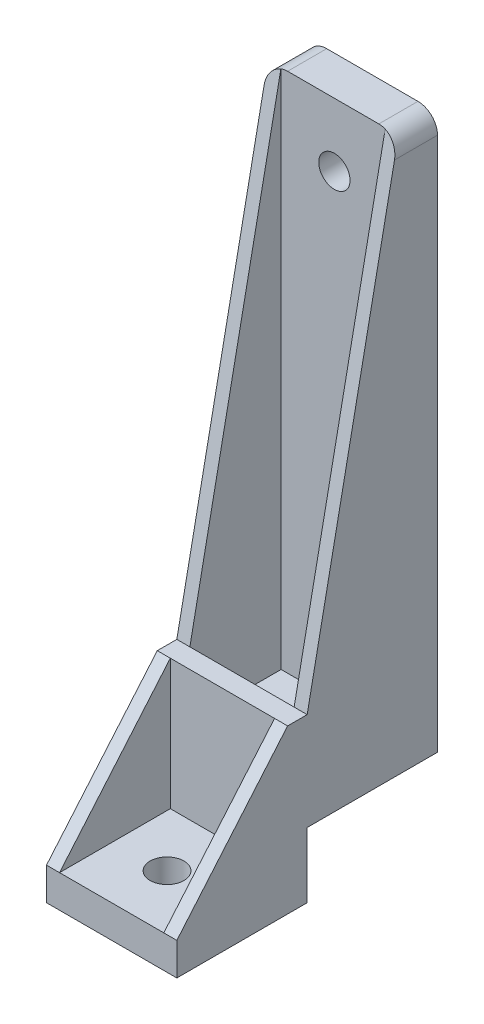
SolidWorks part; units mm, degrees
ref_plane "Front Plane" through (0, 0, 0) normal (0, 0, 1) x (1, 0, 0)
ref_plane "Top Plane" through (0, 0, 0) normal (0, 1, 0) x (1, 0, 0)
ref_plane "Right Plane" through (0, 0, 0) normal (1, 0, 0) x (0, 0, -1)
sketch "Sketch1" plane through (0, 0, 0) normal (0, 1, 0) x (1, 0, 0)
  line L1 (-10, -10) -> (10, -10)
  line L2 (-10, -10) -> (-10, 10)
  line L3 (-10, 10) -> (10, 10)
  line L4 (10, -10) -> (10, 10)
  line L5 (-10, -10) -> (10, 10) construction
  line L6 (-10, 10) -> (10, -10) construction
  point P0 (0, 0)
extrude "Boss-Extrude1" add sketch "Sketch1" along normal blind 5
sketch "Sketch2" plane through (0, 5, 0) normal (0, 1, 0) x (1, 0, 0)
  line L0 (10, -10) -> (10, 10) construction
  line L1 (-10, 10) -> (10, 10)
  line L2 (-10, 10) -> (-10, 7)
  line L3 (-10, 7) -> (10, 7)
  line L4 (10, 10) -> (10, 7)
extrude "Boss-Extrude2" add sketch "Sketch2" along normal blind 20
sketch "Sketch3" plane through (0, 5, 0) normal (0, 1, 0) x (1, 0, 0)
  line L1 (10, -10) -> (10, 7)
  circle A0 centre (0, -1.5) radius 2.6
extrude "Cut-Extrude1" cut sketch "Sketch3" against normal through all and the other way through all contours A0 region at (0, 5, 1.5)
sketch "Sketch4" plane through (-10, 0, 0) normal (-1, 0, 0) x (0, 0, 1)
  line L0 (-7, 25) -> (10, 5)
  line L1 (10, 5) -> (-7, 5)
  line L2 (-7, 5) -> (-7, 25)
extrude "Boss-Extrude3" add sketch "Sketch4" against normal blind 2
sketch "Sketch5" plane through (10, 0, 0) normal (1, 0, 0) x (0, 0, -1)
  line L0 (7, 25) -> (-10, 5)
  line L1 (-10, 5) -> (7, 5)
  line L2 (7, 5) -> (7, 25)
extrude "Boss-Extrude4" add sketch "Sketch5" against normal blind 2
sketch "Sketch6" plane through (0, 0, 0) normal (0, -1, 0) x (-1, 0, 0)
  line L0 (0, -10) -> (0, -8.7973)
  line L1 (10, -10) -> (-10, -10) construction
  line L2 (-10, 10) -> (10, 10) construction
  line L4 (-2, -8.7973) -> (2, -8.7973)
  line L5 (-2, -8.7973) -> (-2, -5.7973)
  line L6 (-2, -5.7973) -> (2, -5.7973)
  line L7 (2, -8.7973) -> (2, -5.7973)
  line L8 (2, 5.7973) -> (2, 2.7973)
  line L9 (-2, 2.7973) -> (2, 2.7973)
  line L11 (0, -5.7973) -> (0, 10)
  line L12 (-2, 5.7973) -> (-2, 2.7973)
  line L13 (-2, 5.7973) -> (2, 5.7973)
  point P6 (0, -7.2973)
extrude "Boss-Extrude5" add sketch "Sketch6" along normal blind 0.8 contours L13 L12 L9 L11 | L13 L11 L9 L8 | L4 L7 L6 L5 region at (0, 0, 7.2973) region at (1, 0, -4.2973) region at (-1, 0, -4.2973)
sketch "Sketch9" plane through (0, 25, 0) normal (0, 1, 0) x (1, 0, 0)
  line L1 (-10, 10) -> (10, 10)
  line L2 (-10, 10) -> (-10, 7)
  line L3 (-10, 7) -> (10, 7)
  line L4 (10, 10) -> (10, 7)
extrude "Boss-Extrude8" add sketch "Sketch9" along normal blind 45
sketch "Sketch12" plane through (0, 0, -10) normal (0, 0, -1) x (-1, 0, 0)
  line L1 (0, 10) -> (-10, 10)
  line L2 (-10, 70) -> (-10, 0) construction
  line L3 (-10, 10) -> (-10, 15)
  line L4 (-10, 15) -> (10, 15)
  line L5 (10, 70) -> (10, 0) construction
  line L6 (10, 15) -> (10, 10)
  line L7 (10, 10) -> (0, 10)
extrude "Boss-Extrude9" add sketch "Sketch12" along normal blind 20
sketch "Sketch13" plane through (0, 15, 0) normal (0, 1, 0) x (1, 0, 0)
  line L0 (10, 30) -> (10, 10) construction
  line L1 (-10, 30) -> (10, 30)
  line L2 (-10, 30) -> (-10, 27)
  line L3 (-10, 27) -> (10, 27)
  line L4 (10, 30) -> (10, 27)
extrude "Boss-Extrude12" add sketch "Sketch13" along normal blind 80
sketch "Sketch16" plane through (-10, 0, 0) normal (-1, 0, 0) x (0, 0, 1)
  line L1 (-10, 70) -> (-7, 70)
  line L2 (-10, 70) -> (-10, 25)
  line L3 (-10, 25) -> (-7, 25)
  line L4 (-7, 70) -> (-7, 25)
extrude "Cut-Extrude3" cut sketch "Sketch16" against normal blind 80
sketch "Sketch22" plane through (0, 0, -27) normal (0, 0, 1) x (1, 0, 0)
  line L1 (-10, 95) -> (10, 95)
  line L2 (-10, 95) -> (-10, 15)
  line L3 (-10, 15) -> (10, 15)
  line L4 (10, 95) -> (10, 15)
extrude "Boss-Extrude15" add sketch "Sketch22" along normal blind 3
sketch "Sketch23" plane through (-10, 0, 0) normal (-1, 0, 0) x (0, 0, 1)
  line L0 (-24, 95) -> (-10, 25)
  line L1 (-10, 25) -> (-10, 15)
  line L2 (-10, 15) -> (-24, 15)
  line L3 (-24, 15) -> (-24, 95)
extrude "Boss-Extrude16" add sketch "Sketch23" against normal blind 2
sketch "Sketch24" plane through (10, 0, 0) normal (1, 0, 0) x (0, 0, -1)
  line L0 (24, 95) -> (10, 25)
  line L1 (10, 25) -> (10, 15)
  line L2 (10, 15) -> (24, 15)
  line L3 (24, 15) -> (24, 95)
extrude "Boss-Extrude17" add sketch "Sketch24" against normal blind 2
fillet "Fillet2" radius 3 2 edges at (-10, 95, -27) (10, 95, -27)
sketch "Sketch26" plane through (0, 0, -30) normal (0, 0, -1) x (-1, 0, 0)
  circle A0 centre (-0.1793, 85.2825) radius 2.4
  circle A1 centre (-0.1793, 20.2825) radius 2.4
extrude "Cut-Extrude5" cut sketch "Sketch26" against normal blind 9
